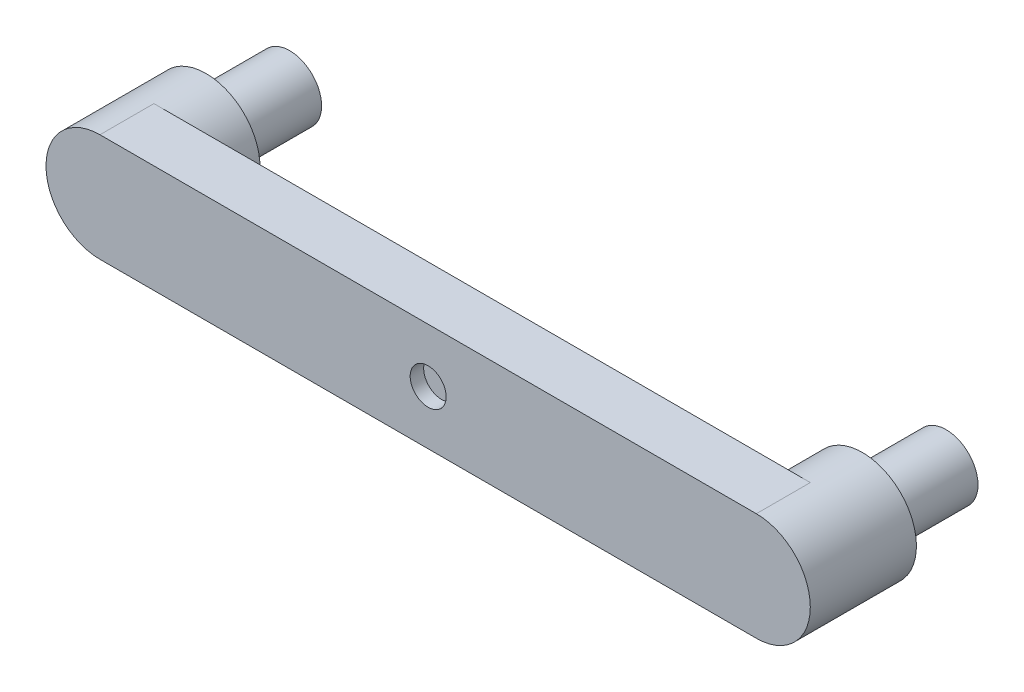
SolidWorks part; units mm, degrees
ref_plane "Front Plane" through (0, 0, 0) normal (0, 0, 1) x (1, 0, 0)
ref_plane "Top Plane" through (0, 0, 0) normal (0, 1, 0) x (1, 0, 0)
ref_plane "Right Plane" through (0, 0, 0) normal (1, 0, 0) x (0, 0, -1)
sketch "Sketch1" plane through (0, 0, 0) normal (0, 0, 1) x (1, 0, 0)
  line L0 (-182.5, 0) -> (182.5, 0) construction
  line L1 (-182.5, 30) -> (182.5, 30)
  line L2 (-182.5, -30) -> (182.5, -30)
  arc A0 (-182.5, 30) -> (-182.5, -30) centre (-182.5, 0) ccw
  arc A1 (182.5, -30) -> (182.5, 30) centre (182.5, 0) ccw
  circle A2 centre (0, 0) radius 10
  circle A3 centre (182.5, 0) radius 17.75
  circle A4 centre (-182.5, 0) radius 17.75
  point P2 (0, 0)
  dimension "D1" = 20
  dimension "D2" = 35.5
  dimension "D3" = 30
  dimension "D4" = 365
extrude "Boss-Extrude1" add sketch "Sketch1" against normal blind 30 contours A4 | L2 A1 L1 A0 A4 A2 A3 | A2 L0 | L0 A2 | A3 region at (182.5, 17.248, 0) region at (0, 4.2441, 0) region at (0, -4.2441, 0) region at (-199.748, 0, 0) region at (0, 25.7079, 0)
sketch "Sketch2" plane through (0, 0, -30) normal (0, 0, -1) x (-1, 0, 0)
  circle A1 centre (-182.5, 0) radius 30
  circle A2 centre (182.5, 0) radius 30
  arc A3 (-182.5, 30) -> (-182.5, -30) centre (-182.5, 0) ccw construction
  arc A4 (182.5, -30) -> (182.5, 30) centre (182.5, 0) ccw construction
extrude "Boss-Extrude2" add sketch "Sketch2" along normal blind 29
extrude "Cut-Extrude1" cut sketch "Sketch1<3>" against normal up to surface (30 mm away) contours A2 L0 | L0 A2 region at (0, 4.2441, 0) region at (0, -4.2441, 0) up to face at (0, 0, -30)
sketch "Sketch1<3>" plane through (0, 0, 0) normal (0, 0, 1) x (1, 0, 0) same geometry as "Sketch1"
extrude "Boss-Extrude3" add sketch "Sketch1<4>" against normal blind 46.5 from surface contours A3 | A4 region at (182.5, 0, 0) region at (-182.5, 0, 0) starting at face at (152.5, 0, -59)
sketch "Sketch1<4>" plane through (0, 0, 0) normal (0, 0, 1) x (1, 0, 0) same geometry as "Sketch1"
sketch "Sketch3" plane through (0, -30, 0) normal (0, -1, 0) x (1, 0, 0)
  line L0 (182.5, -30) -> (182.5, 0) construction
  line L1 (-30, -22.5) -> (30, -22.5)
  line L2 (-30, -22.5) -> (-30, -7.5)
  line L3 (-30, -7.5) -> (30, -7.5)
  line L4 (30, -22.5) -> (30, -7.5)
  point P4 (0, -7.5)
  point P8 (182.5, -15)
  point P9 (30, -15)
  dimension "D1" = 15
  dimension "D2" = 60
extrude "Cut-Extrude2" cut sketch "Sketch3" against normal blind 45
